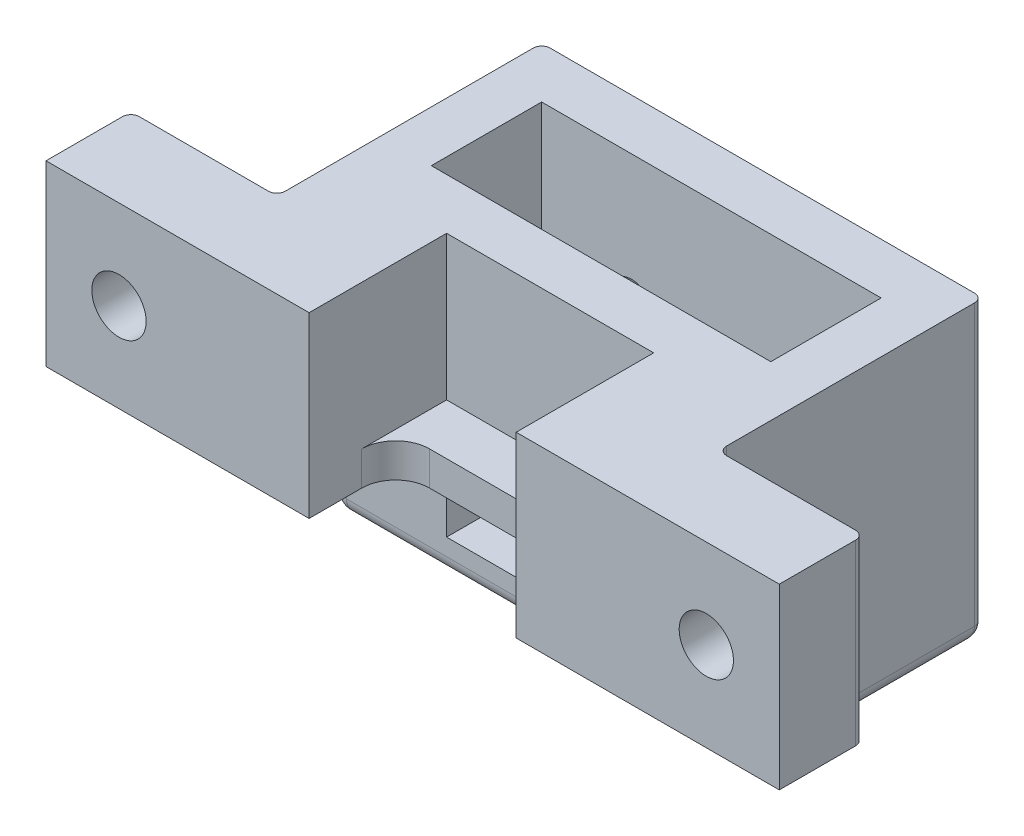
SolidWorks part; units mm, degrees
ref_plane "Front Plane" through (0, 0, 0) normal (0, 0, 1) x (1, 0, 0)
ref_plane "Top Plane" through (0, 0, 0) normal (0, 1, 0) x (1, 0, 0)
ref_plane "Right Plane" through (0, 0, 0) normal (1, 0, 0) x (0, 0, -1)
sketch "Sketch1" plane through (0, 0, 0) normal (0, 1, 0) x (1, 0, 0)
  line L0 (0, 0) -> (0, 8.1)
  line L1 (0, 8.1) -> (12.2, 8.1)
  line L2 (12.2, 8.1) -> (12.2, 0)
  line L3 (-15.5, 0) -> (-15.5, 4.5)
  line L4 (16.1, 11.1) -> (-3.9, 11.1)
  line L5 (-3.9, 11.1) -> (-3.9, 17.6)
  line L6 (-3.9, 17.6) -> (16.1, 17.6)
  line L7 (16.1, 17.6) -> (16.1, 11.1)
  line L8 (18.6, 20.6) -> (-6.4, 20.6)
  line L9 (-15, 5) -> (-7.4, 5)
  line L10 (27.7, 0) -> (27.7, 4.5)
  line L11 (27.2, 5) -> (19.6, 5)
  line L12 (0, 0) -> (-15.5, 0)
  line L13 (12.2, 0) -> (27.7, 0)
  line L14 (-6.9, 20.1) -> (-6.9, 5.5)
  line L17 (19.1, 20.1) -> (19.1, 5.5)
  arc A0 (27.7, 4.5) -> (27.2, 5) centre (27.2, 4.5) ccw
  arc A1 (-15.5, 4.5) -> (-15, 5) centre (-15, 4.5) cw
  arc A2 (-6.9, 5.5) -> (-7.4, 5) centre (-7.4, 5.5) cw
  arc A3 (19.1, 5.5) -> (19.6, 5) centre (19.6, 5.5) ccw
  arc A4 (19.1, 20.1) -> (18.6, 20.6) centre (18.6, 20.1) ccw
  arc A5 (-6.4, 20.6) -> (-6.9, 20.1) centre (-6.4, 20.1) ccw
  dimension "D1" = 0.5
extrude "Boss-Extrude1" add sketch "Sketch1" along normal blind 10.5
sketch "Sketch4" plane through (0, 0, -20.6) normal (0, 0, -1) x (-1, 0, 0)
  circle A1 centre (-11.1, 2.85) radius 1.25
  circle A2 centre (-1.4, 2.85) radius 1.25
extrude "Cut-Extrude1" cut sketch "Sketch4" against normal up to next
sketch "Sketch5" plane through (0, 0, 0) normal (0, -1, 0) x (1, 0, 0)
  line L0 (12.2, -8.1) -> (19.1, -8.1)
  line L1 (19.1, -5.5) -> (19.1, -20.1) construction
  line L2 (19.1, -8.1) -> (19.1, -20.1)
  line L3 (-6.4, -20.6) -> (18.6, -20.6)
  line L4 (0, -8.1) -> (0, -11.1)
  line L5 (-6.9, -8.1) -> (-6.9, -20.1)
  line L6 (-6.9, -20.1) -> (-6.9, -5.5) construction
  line L7 (0, -8.1) -> (-6.9, -8.1)
  line L8 (-3.9, -11.1) -> (16.1, -11.1) construction
  line L9 (0, -11.1) -> (-3.9, -11.1)
  line L10 (-3.9, -11.1) -> (-3.9, -17.6)
  line L11 (-3.9, -17.6) -> (16.1, -17.6)
  line L12 (16.1, -17.6) -> (16.1, -11.1)
  line L13 (16.1, -11.1) -> (12.2, -11.1)
  line L14 (12.2, -11.1) -> (12.2, -8.1)
  arc A0 (19.1, -20.1) -> (18.6, -20.6) centre (18.6, -20.1) cw
  arc A1 (-6.9, -20.1) -> (-6.4, -20.6) centre (-6.4, -20.1) ccw
  dimension "D1" = 0.5
extrude "Boss-Extrude2" add sketch "Sketch5" along normal blind 5
sketch "Sketch6" plane through (0, -5, 0) normal (0, -1, 0) x (1, 0, 0)
  line L0 (-6.9, -8.1) -> (19.1, -8.1)
  line L1 (19.1, -8.1) -> (19.1, -20.1)
  line L2 (-6.9, -8.1) -> (-6.9, -20.1)
  line L3 (-6.4, -20.6) -> (18.6, -20.6)
  arc A0 (19.1, -20.1) -> (18.6, -20.6) centre (18.6, -20.1) cw
  arc A1 (-6.4, -20.6) -> (-6.9, -20.1) centre (-6.4, -20.1) cw
  dimension "D1" = 0.5
extrude "Boss-Extrude3" add sketch "Sketch6" along normal blind 2
fillet "Fillet1" radius 1 8 edges at (-6.9, -7, -14.1) (-6.7536, -7, -20.4536) (19.1, -7, -14.1) (18.9536, -7, -20.4536) (6.1, -7, -8.1) (6.1, -7, -20.6)
sketch "Sketch7" plane through (0, 0, -8.1) normal (0, 0, 1) x (1, 0, 0)
  line L0 (0, 0) -> (0, 2)
  line L1 (0, 10.5) -> (0, 0) construction
  line L2 (0, 2) -> (12.2, 2)
  line L3 (12.2, 10.5) -> (12.2, 0) construction
  line L4 (12.2, 2) -> (12.2, 0)
  line L5 (12.2, 0) -> (0, 0)
extrude "Boss-Extrude5" add sketch "Sketch7" along normal blind 3
fillet "Fillet2" radius 2 2 edges at (12.2, 1, -5.1) (0, 1, -5.1)
sketch "Sketch8" plane through (0, 0, -5) normal (0, 0, -1) x (-1, 0, 0)
  circle A0 centre (-23.4, 5.25) radius 1.6
  circle A1 centre (11.2, 5.25) radius 1.6
extrude "Cut-Extrude2" cut sketch "Sketch8" against normal up to next
